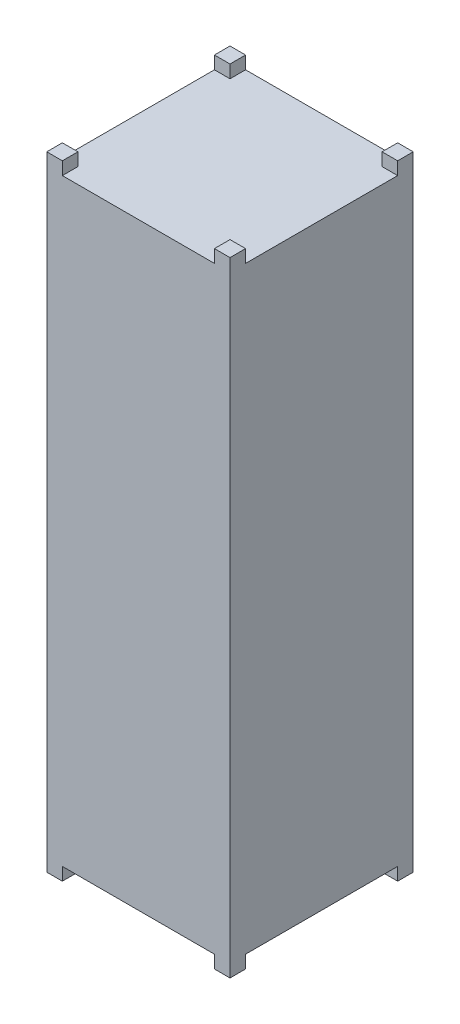
SolidWorks part; units mm, degrees
ref_plane "Alzado" through (0, 0, 0) normal (0, 0, 1) x (1, 0, 0)
ref_plane "Planta" through (0, 0, 0) normal (0, 1, 0) x (1, 0, 0)
ref_plane "Vista lateral" through (0, 0, 0) normal (1, 0, 0) x (0, 0, -1)
sketch "CubeSat" plane through (0, 0, 0) normal (0, 1, 0) x (1, 0, 0)
  line L0 (0, 0) -> (0, 50) construction
  line L1 (-50, -50) -> (50, -50)
  line L2 (-50, -50) -> (-50, 50)
  line L3 (-50, 50) -> (50, 50)
  line L4 (50, -50) -> (50, 50)
  line L5 (-50, -50) -> (50, 50) construction
  line L6 (-50, 50) -> (50, -50) construction
  line L7 (-50, 50) -> (-40.7285, 50)
  line L8 (-50, 50) -> (-50, 40.7285)
  line L11 (0, 0) -> (-50, 0) construction
  line L12 (50, 41.5) -> (41.5, 41.5)
  line L13 (-50, 50) -> (-41.5, 50)
  line L14 (-50, 50) -> (-50, 41.5)
  line L15 (-50, 41.5) -> (-41.5, 41.5)
  line L16 (-41.5, 50) -> (-41.5, 41.5)
  line L17 (41.5, 50) -> (41.5, 41.5)
  line L18 (41.5, -50) -> (41.5, -41.5)
  line L19 (50, -41.5) -> (41.5, -41.5)
  line L20 (-41.5, -50) -> (-41.5, -41.5)
  line L21 (-50, -41.5) -> (-41.5, -41.5)
  circle A0 centre (0, 0) radius 11.5 construction
  point P0 (0, 0)
  dimension "D1" = 100
  dimension "D2" = 100
  dimension "D3" = 8.5
  dimension "D4" = 8.5
extrude "BODY" add sketch "CubeSat" along normal blind 326.5 from offset 7 contours L2 L21 L20 L1 L18 L19 L4 L12 L17 L3 L7 L16 L15 region at (0, 0, 0)
extrude "Rail" add sketch "CubeSat<3>" along normal blind 340.5 contours L21 L2 L1 L20 | L16 L3 L8 L15 | L4 L19 L18 L1 | L3 L17 L12 L4 region at (-45.75, 0, 45.75) region at (45.75, 0, 45.75) region at (-45.75, 0, -45.75) region at (45.75, 0, -45.75)
sketch "CubeSat<3>" plane through (0, 0, 0) normal (0, 1, 0) x (1, 0, 0) same geometry as "CubeSat"
